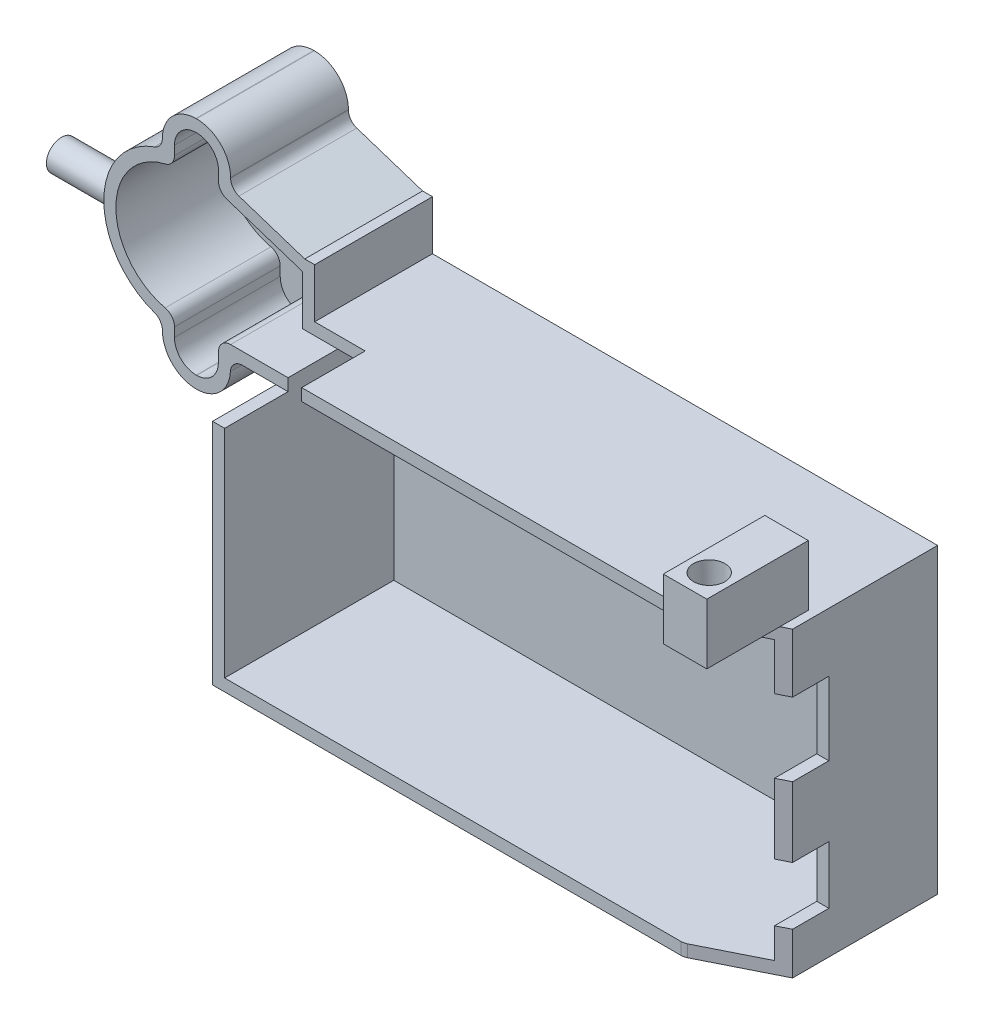
SolidWorks part; units mm, degrees
ref_plane "Front Plane" through (0, 0, 0) normal (0, 0, 1) x (1, 0, 0)
ref_plane "Top Plane" through (0, 0, 0) normal (0, 1, 0) x (1, 0, 0)
ref_plane "Right Plane" through (0, 0, 0) normal (1, 0, 0) x (0, 0, -1)
sketch "Sketch1" plane through (0, 0, 0) normal (0, 0, 1) x (1, 0, 0)
  line L1 (-57.15, -31.75) -> (57.15, -31.75)
  line L4 (57.15, -31.75) -> (57.15, 31.75)
  line L8 (57.15, 31.75) -> (-49.022, 31.75)
  line L10 (-57.15, -31.75) -> (-57.15, 16.2416)
  line L16 (-73.8551, 41.8347) -> (-73.8551, 45.5747) construction
  line L25 (-73.8551, 45.5747) -> (-73.8551, 41.8347) construction
  line L26 (-73.9116, 14.1747) -> (-73.7985, 14.1747) construction
  line L27 (-81.0236, 49.1747) -> (-81.0236, 47.2491)
  line L28 (-66.6865, 49.1747) -> (-66.6865, 47.2491)
  line L29 (-73.9116, 7.0627) -> (-73.7985, 7.0627)
  line L30 (-73.9682, 56.2865) -> (-73.8551, 56.2865)
  line L31 (-81.0236, 16.1003) -> (-81.0236, 14.1747)
  line L32 (-66.688, 16.2416) -> (-66.7283, 14.3164)
  line L34 (-73.9116, 49.1747) -> (-73.7985, 49.1747) construction
  line L35 (-73.8551, 14.1747) -> (-73.8551, 49.1747) construction
  line L37 (-51.1008, 42.1449) -> (-66.6865, 47.2491)
  line L38 (-51.1008, 42.1449) -> (-49.022, 42.1449)
  line L39 (-49.022, 42.1449) -> (-49.022, 31.75)
  line L40 (-66.688, 16.2416) -> (-57.15, 16.2416)
  arc A0 (-66.7283, 14.3164) -> (-73.7985, 7.0627) centre (-73.8389, 14.1746) cw
  arc A1 (-81.0236, 14.1747) -> (-73.9116, 7.0627) centre (-73.9116, 14.1747) ccw
  arc A2 (-66.6865, 49.1747) -> (-73.8551, 56.2865) centre (-73.7985, 49.1747) ccw
  arc A3 (-81.0236, 49.1747) -> (-73.9682, 56.2865) centre (-73.9116, 49.1747) cw
  arc A4 (-81.0236, 47.2491) -> (-81.0236, 16.1003) centre (-77.337, 31.6747) ccw
  point P0 (0, 0)
  point P23 (-70.3732, 31.6747)
  point P28 (-77.337, 31.6747)
  point P29 (-73.8551, 31.6747)
  point P34 (-73.8551, 31.6747)
  dimension "D1" = 31.75
  dimension "D2" = 63.5
  dimension "D5" = 114.3
  dimension "D7" = 57.15
extrude "Boss-Extrude1" add sketch "Sketch1" along normal mid plane 38.1
shell "Shell3" thickness 2.54 removed face at (-55.1484, 25.3107, 19.05)
sketch "Sketch7" plane through (0, 31.75, 0) normal (0, 1, 0) x (1, 0, 0)
  line L0 (57.15, -19.05) -> (-49.022, -19.05) construction
  line L2 (55.372, -27.686) -> (55.372, -6.35)
  line L3 (55.372, -6.35) -> (46.228, -6.35)
  line L4 (46.228, -6.35) -> (46.228, -27.686)
  line L5 (46.228, -27.686) -> (55.372, -27.686)
  circle A0 centre (50.8, -22.606) radius 3.302
  point P0 (0, 0)
  point P7 (50.8, -19.05)
  dimension "D5" = 6.604
  dimension "D6" = 4.572
  dimension "D1" = 6.35
  dimension "D2" = 9.144
  dimension "D3" = 12.7
  dimension "D4" = 3.556
  dimension "D7" = 5.08
extrude "Boss-Extrude3" add sketch "Sketch7" along normal blind 12.7
fillet "Chamfer1" radius 7.62 1 edges at (57.15, 0, 19.05) profile chamfer first distance on face at (57.15, 0, 0)
sketch "Sketch8" plane through (0, 0, 19.05) normal (0, 0, 1) x (1, 0, 0)
  line L13 (-66.6105, 49.0028) -> (-66.6105, 47.2793)
  line L14 (-66.688, 16.2416) -> (-38.4037, 16.2416)
  line L15 (-38.4037, 16.2416) -> (-38.4037, 42.1449)
  line L22 (-38.4037, 42.1449) -> (-51.1008, 42.1449)
  line L29 (-73.9116, 49.1747) -> (-73.7985, 49.1747) construction
  line L30 (-74.2559, 14.1963) -> (-73.8551, 49.1747) construction
  line L35 (-51.1008, 42.1449) -> (-66.6105, 47.2793)
  line L37 (-81.0236, 49.1747) -> (-81.0236, 47.2491)
  line L38 (-81.0236, 14.1747) -> (-81.0236, 16.1003)
  line L39 (-66.688, 16.2416) -> (-66.7269, 14.1746)
  arc A16 (-66.7269, 14.1746) -> (-71.1088, 7.4772) centre (-73.9621, 14.1262) cw
  arc A17 (-81.0236, 47.2491) -> (-81.0236, 16.1003) centre (-77.337, 31.6747) ccw
  arc A19 (-73.7985, 7.0627) -> (-66.7283, 14.3164) centre (-73.8389, 14.1746) ccw construction
  arc A20 (-81.0236, 14.1747) -> (-71.1088, 7.4772) centre (-73.9135, 14.0128) ccw
  arc A25 (-78.7889, 54.3509) -> (-81.0236, 49.1747) centre (-73.9116, 49.1747) ccw
  arc A26 (-66.6105, 49.0028) -> (-78.7889, 54.3509) centre (-73.7985, 49.1747) ccw
  point P18 (-79.6902, 31.6747)
  point P23 (-68.02, 31.6747)
  point P24 (-73.8551, 31.6747)
  point P27 (-74.0555, 31.6855)
extrude "Cut-Extrude4" cut sketch "Sketch8" against normal blind 13.335
ref_plane "Plane1" through (-93.3418, 0, 0) normal (1, 0, 0) x (0, 0, -1)
sketch "Sketch9" plane through (-93.3418, 0, 0) normal (1, 0, 0) x (0, 0, -1)
  line L3 (-5.715, 47.2491) -> (-5.715, 16.1003) construction
  circle A1 centre (-1.905, 31.75) radius 3.175
  dimension "D1" = 3.81
  dimension "D2" = 6.35
extrude "Boss-Extrude4" add sketch "Sketch9" along normal blind 1.27 and the other way blind 12.7
sketch "Sketch10" plane through (57.15, 0, 0) normal (1, 0, 0) x (0, 0, -1)
  line L1 (-19.05, -29.21) -> (-13.3141, -29.21)
  line L2 (-19.05, -29.21) -> (-19.05, 29.21)
  line L3 (-19.05, 29.21) -> (-13.3141, 29.21)
  line L5 (-3.81, -10.7291) -> (-13.3141, -10.7291)
  line L7 (-13.3141, -10.7291) -> (-13.3141, 3.9747)
  line L8 (-13.3141, 3.9747) -> (-3.81, 3.9747)
  line L10 (-3.81, 3.9747) -> (-3.81, 19.3661)
  line L11 (-3.81, 19.3661) -> (-13.3141, 19.3661)
  line L12 (-13.3141, 19.3661) -> (-13.3141, 29.21)
  line L13 (-3.81, -10.7291) -> (-3.81, -22.8781)
  line L14 (-3.81, -22.8781) -> (-13.3141, -22.8781)
  line L15 (-13.3141, -22.8781) -> (-13.3141, -29.21)
extrude "Cut-Extrude5" cut sketch "Sketch10" against normal up to surface (2.54 mm away) up to face at (54.61, 0, -1.905)
fillet "Fillet1" radius 2.54 8 edges at (-81.0236, 16.1003, -6.6675) (-78.4836, 18.2588, -5.3975) (-69.1753, 18.7816, -5.3975) (-66.688, 16.2416, -6.6675) (-69.2265, 45.4082, -5.3975) (-66.6865, 47.2491, -6.6675) (-81.0236, 47.2491, -6.6675) (-78.4836, 45.0906, -5.3975)
fillet "Fillet2" radius 2.54 2 edges at (41.91, -30.48, 19.05) (41.91, 30.48, 19.05)
